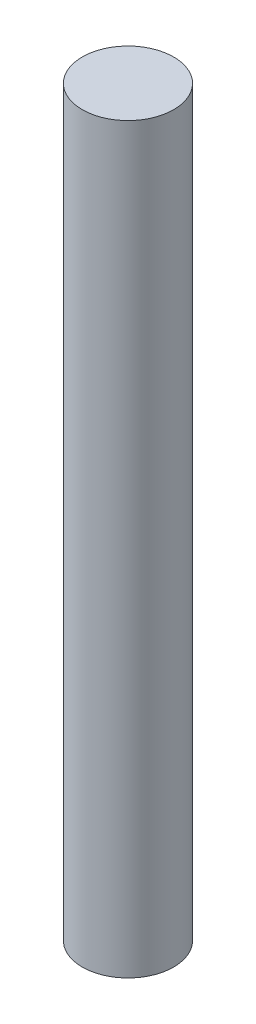
SolidWorks part; units mm, degrees
ref_plane "Спереди" through (0, 0, 0) normal (0, 0, 1) x (1, 0, 0)
ref_plane "Сверху" through (0, 0, 0) normal (0, 1, 0) x (1, 0, 0)
ref_plane "Справа" through (0, 0, 0) normal (1, 0, 0) x (0, 0, -1)
sketch "Эскиз1" plane through (0, 0, 0) normal (0, 1, 0) x (1, 0, 0)
  circle A0 centre (0, 0) radius 4
  dimension "D1" = 8
extrude "Бобышка-Вытянуть1" add sketch "Эскиз1" along normal blind 65
